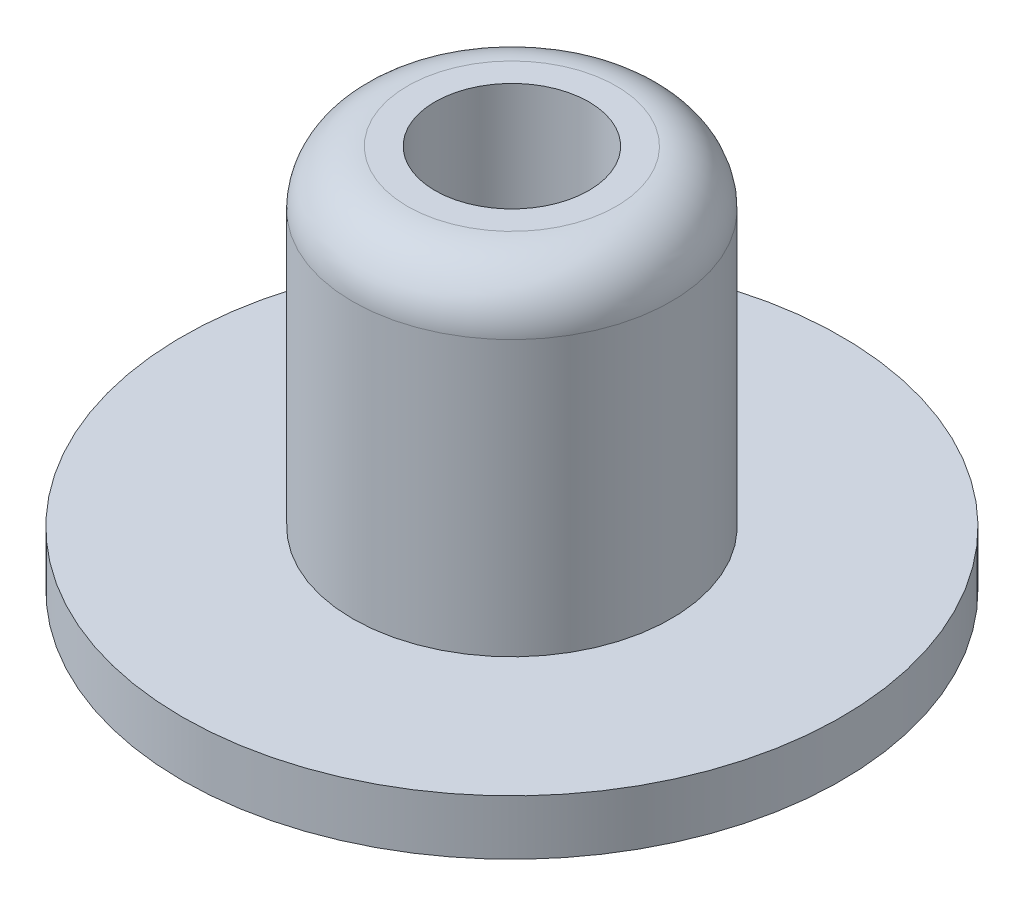
SolidWorks part; units mm, degrees
material "PET"
ref_plane "Front Plane" through (0, 0, 0) normal (0, 0, 1) x (1, 0, 0)
ref_plane "Top Plane" through (0, 0, 0) normal (0, 1, 0) x (1, 0, 0)
ref_plane "Right Plane" through (0, 0, 0) normal (1, 0, 0) x (0, 0, -1)
sketch "Sketch1" plane through (0, 0, 0) normal (0, 1, 0) x (1, 0, 0)
  circle A0 centre (0, 0) radius 3.5
  circle A1 centre (0, 0) radius 7.25
  dimension "D1" = 7
  dimension "D2" = 14.5
extrude "Boss-Extrude1" add sketch "Sketch1" along normal blind 15
sketch "Sketch2" plane through (0, 0, 0) normal (0, -1, 0) x (1, 0, 0)
  circle A0 centre (0, 0) radius 3.5
  circle A1 centre (0, 0) radius 10
  dimension "D1" = 20
extrude "Boss-Extrude2" add sketch "Sketch2" along normal blind 5
sketch "Sketch3" plane through (0, 0, 0) normal (0, 1, 0) x (1, 0, 0)
  circle A0 centre (0, 0) radius 3.5
  circle A1 centre (0, 0) radius 15
extrude "Boss-Extrude3" add sketch "Sketch3" against normal blind 2.5
fillet "Fillet1" radius 5 1 edges at (0, -2.5, 10)
fillet "Fillet2" radius 2.5 1 edges at (0, 15, 7.25)
fillet "Fillet3" radius 2.5 1 edges at (0, -5, -3.5)
